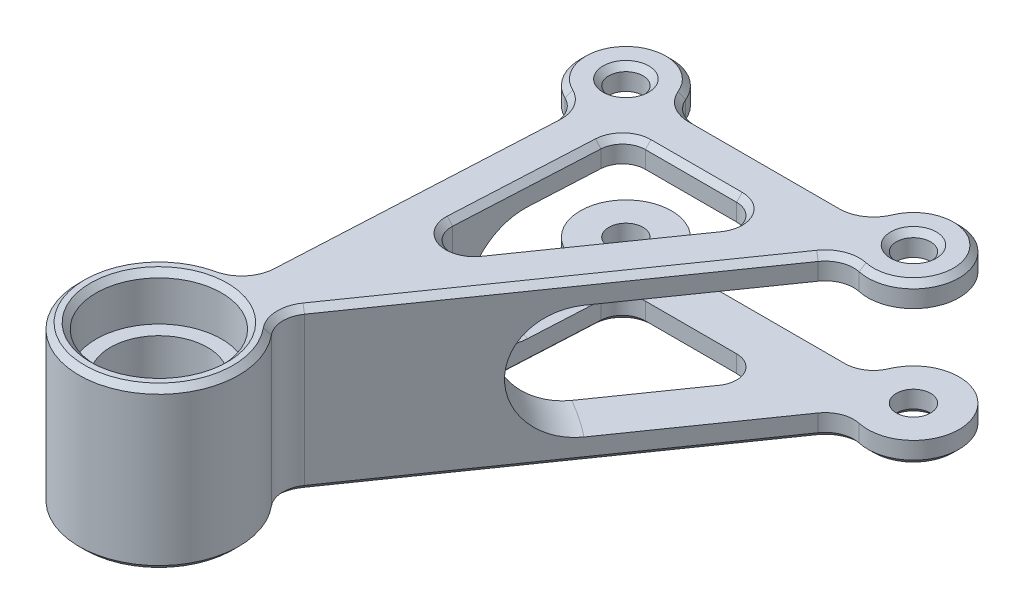
SolidWorks part; units mm, degrees
note: '?' marks a value the reader was unsure of.
other "Markup1"
sketch "Sketch11" plane through (62.376, 14, -85.899) normal (0.024, 0.981, -0.1925) x (0.9934, -0.0451, -0.1056)
material "7075-O (SS)"
ref_plane "Front Plane" through (0, 0, 0) normal (0, 0, 1) x (1, 0, 0)
ref_plane "Top Plane" through (0, 0, 0) normal (0, 1, 0) x (1, 0, 0)
ref_plane "Right Plane" through (0, 0, 0) normal (1, 0, 0) x (0, 0, -1)
sketch "Sketch1" plane through (0, 0, 0) normal (0, 1, 0) x (1, 0, 0)
  circle A0 centre (0, 0) radius 14
  dimension "D1" = 28
extrude "Boss-Extrude1" add sketch "Sketch1" along normal mid plane 28
sketch "Sketch4" plane through (0, 14, 0) normal (0, 1, 0) x (1, 0, 0)
  circle A0 centre (0, 0) radius 11
  dimension "D1" = 22
extrude "Cut-Extrude1" cut sketch "Sketch4" against normal blind 8
mirror "Mirror1" about plane through (0, 0, 0) normal (0, 1, 0) of "Cut-Extrude1"
sketch "Sketch5" plane through (0, 6, 0) normal (0, 1, 0) x (1, 0, 0)
  circle A0 centre (0, 0) radius 8.5
  dimension "D1" = 17
extrude "Cut-Extrude2" cut sketch "Sketch5" against normal through all
sketch "Sketch6" plane through (0, 0, 0) normal (0, 1, 0) x (1, 0, 0)
  line L0 (0, 0) -> (49.797, 71.3391)
  line L1 (46.376, 77.899) -> (11.9684, 77.899)
  line L2 (3.5614, 69.9093) -> (0, 0)
  line L3 (9.4091, 27.4562) -> (39.0355, 69.899)
  line L4 (39.0355, 69.899) -> (11.5712, 69.899)
  line L5 (11.5712, 69.899) -> (9.4091, 27.4562)
  line L7 (54.376, 77.899) -> (3.9684, 77.899) construction
  line L8 (3.9684, 77.899) -> (0, 0) construction
  line L9 (0, 0) -> (54.376, 77.899) construction
  arc A0 (11.9684, 77.899) -> (3.5614, 69.9093) centre (3.9684, 77.899) ccw
  arc A1 (49.797, 71.3391) -> (46.376, 77.899) centre (54.376, 77.899) ccw
  dimension "D6" = 16
  dimension "D1" = 95
  dimension "D2" = 78
  dimension "D4" = 32
  dimension "D3" = 8
extrude "Boss-Extrude2" add sketch "Sketch6" along normal up to surface and the other way up to surface up to face at (0, 14, 11) other way up to face at (0, -14, 11)
sketch "Sketch7" plane through (0, 0, 0) normal (0, 0, 1) x (1, 0, 0)
  line L0 (0, 14) -> (0, -14)
  line L1 (0, 14) -> (11, 14)
  line L2 (11, 14) -> (11, 6)
  line L3 (11, 6) -> (8.5, 6)
  line L4 (8.5, 6) -> (8.5, -6)
  line L5 (8.5, -6) -> (11, -6)
  line L6 (11, -6) -> (11, -14)
  line L7 (11, -14) -> (0, -14)
revolve "Cut-Revolve1" cut sketch "Sketch7" angle 360 about L0
sketch "Sketch8" plane through (0, 0, 0) normal (0, 1, 0) x (1, 0, 0)
  circle A0 centre (3.9684, 77.899) radius 3
  circle A1 centre (54.376, 77.899) radius 3
  dimension "D1" = 6
extrude "Cut-Extrude3" cut sketch "Sketch8" against normal through all both and the other way through all
fillet "Fillet1" radius 5 6 edges at (8.0133, 0, -11.4799) (0.7123, 0, -13.9819) (3.5614, 0, -69.9093) (49.797, 0, -71.3391) (46.376, 0, -77.899) (11.9684, 0, -77.899)
fillet "Fillet2" radius 4 3 edges at (39.0355, 0, -69.899) (11.5712, 0, -69.899) (9.4091, 0, -27.4562)
ref_plane "Plane1" through (-4.0316, 0, 0) normal (-1, 0, 0) x (0, 0, 1)
sketch "Sketch10" plane through (-4.0316, 0, 0) normal (-1, 0, 0) x (0, 0, 1)
  line L0 (-115.899, 10) -> (-55.899, 10)
  line L2 (-55.899, 10) -> (-55.899, -10) construction
  line L3 (-55.899, -10) -> (-115.899, -10)
  line L4 (0, 0) -> (-55.899, 0) construction
  line L6 (0.1618, 14) -> (0.1618, -14) construction
  line L7 (14, 14) -> (-13.6765, 14) construction
  line L8 (-13.6765, -14) -> (14, -14) construction
  line L9 (-115.899, 10) -> (-115.899, -10)
  arc A0 (-55.899, 10) -> (-55.899, -10) centre (-55.899, 0) cw
  dimension "D1" = 10
  dimension "D2" = 30
  dimension "D3" = 30
revolve "Cut-Revolve2" cut sketch "Sketch10" angle 360 about L6
chamfer "Chamfer1" distance 1 angle 45 42 edges at (45.1495, -14, -78.7387) (45.1495, 14, -78.7387) (13.1949, -14, -78.7387) (13.1949, 14, -78.7387) (26.0194, 14, -51.2521) (26.0194, -14, -51.2521) (23.3689, 14, -69.899) (23.3689, -14, -69.899) (10.7483, 14, -53.7451) (10.7483, -14, -53.7451) (34.912, -14, -67.7486) (34.912, 14, -67.7486) (12.6171, -14, -68.7985) (12.6171, 14, -68.7985) (12.8168, -14, -37.4003) (12.8168, 14, -37.4003) (0, -14, 11) (0, 14, 11) (3.9684, -14, -74.899) (3.9684, 14, -74.899) (54.376, -14, -74.899) (54.376, 14, -74.899) (28.9997, 14, -41.5449) (28.9997, -14, -41.5449) (-4.5386, 14, 13.2439) (-4.5386, -14, 13.2439) (2.1452, -14, -42.1105) (2.1452, 14, -42.1105) (-1.5427, 14, -83.698) (-1.5427, -14, -83.698) (61.4694, 14, -81.5982) (61.4694, -14, -81.5982) (29.1722, 14, -77.899) (29.1722, -14, -77.899) (9.5964, -14, -11.9546) (9.5964, 14, -11.9546) (-0.2469, 14, -15.3278) (-0.2469, -14, -15.3278) (2.6603, -14, -68.7272) (2.6603, 14, -68.7272) (49.7835, -14, -69.8527) (49.7835, 14, -69.8527)
ref_plane "Plane2" through (11.4799, 0, 8.0133) normal (0.82, 0, 0.5724) x (0.5724, 0, -0.82)
ref_axis "Axis1" through (3.9684, -13, -77.899) along (0, 1, 0)?
ref_axis "Axis2" through (3.9684, 10, -77.899) along (0, 1, 0)?
ref_axis "Axis3" through (0, -6, 0) along (0, 1, 0)?
